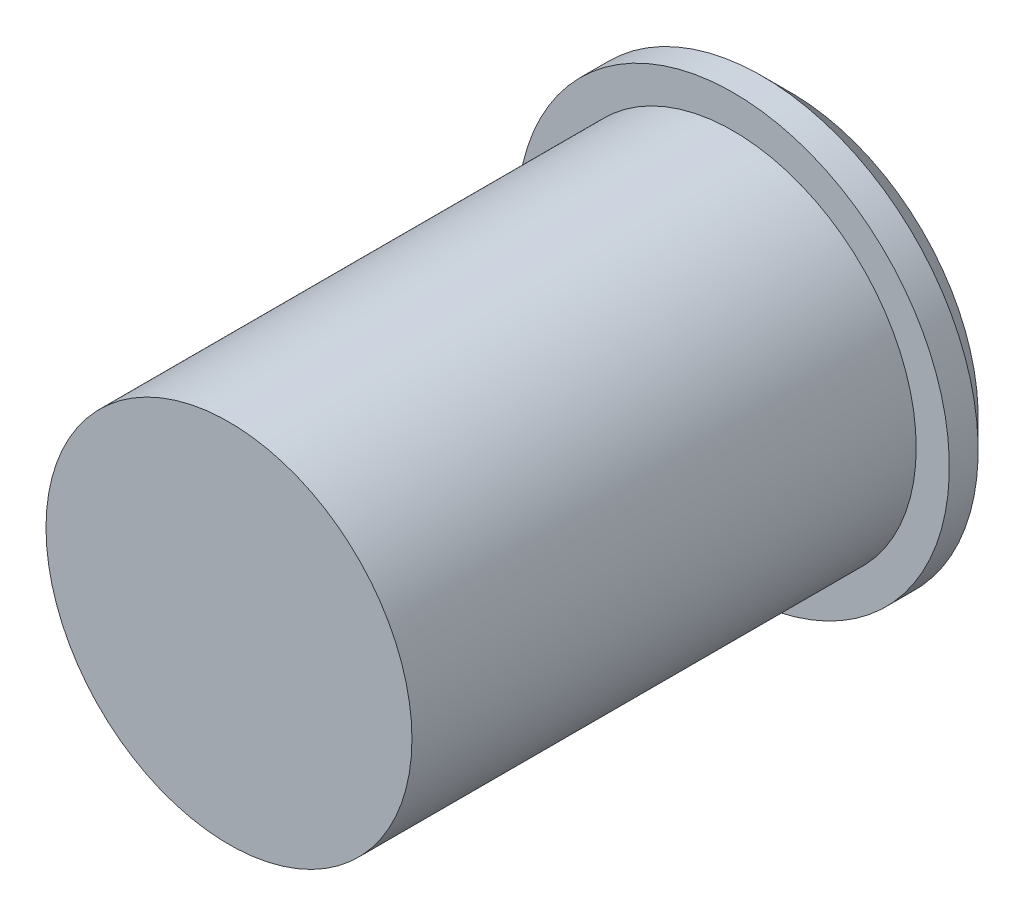
SolidWorks part; units mm, degrees
ref_plane "Front Plane" through (0, 0, 0) normal (0, 0, 1) x (1, 0, 0)
ref_plane "Top Plane" through (0, 0, 0) normal (0, 1, 0) x (1, 0, 0)
ref_plane "Right Plane" through (0, 0, 0) normal (1, 0, 0) x (0, 0, -1)
sketch "Sketch1" plane through (0, 0, 0) normal (0, 1, 0) x (1, 0, 0)
  line L0 (0, 0) -> (6.35, 0)
  line L1 (6.35, 0) -> (6.35, 17.5)
  line L2 (6.35, 17.5) -> (7.5, 17.5)
  line L3 (7.5, 17.5) -> (7.5, 18.5)
  line L4 (7.5, 18.5) -> (6.5, 19.5)
  line L5 (6.5, 19.5) -> (0, 19.5)
  line L6 (0, 19.5) -> (0, 0)
  line L7 (-7.5, 18.5) -> (-6.5, 19.5) construction
  line L8 (-7.5, 17.5) -> (-7.5, 18.5) construction
  line L9 (-6.35, 17.5) -> (-7.5, 17.5) construction
  line L10 (-6.35, 0) -> (-6.35, 17.5) construction
  line L11 (-6.5, 19.5) -> (-7.5, 19.5) construction
  line L12 (-7.5, 19.5) -> (-7.5, 18.5) construction
  line L13 (7.5, 18.5) -> (-7.5, 18.5) construction
  line L14 (-6.5, 19.5) -> (0, 19.5) construction
  line L15 (-6.35, 0) -> (0, 0) construction
  dimension "D1" = 15
  dimension "D2" = 2
  dimension "D3" = 17.5
  dimension "D4" = 45
  dimension "D5" = 12.7
revolve "Revolve2" add sketch "Sketch1" angle 360 about L6
sketch "Sketch2" plane through (0, 0, -19.5) normal (0, 0, -1) x (-1, 0, 0)
  point P0 (0, 0)
hole_wizard "3/8 (0.375) Diameter Hole1" positions "Sketch4" profile "Sketch5" hole size "3/8" standard "ANSI Inch"
sketch "Sketch4" plane through (0, 0, -19.5) normal (0, 0, -1) x (-1, 0, 0)
  point P0 (0, 0)
sketch "Sketch5" plane through (0, 0, -19.5) normal (1, 0, 0) x (0, 1, 0)
  line L0 (0, 0) -> (0, 8.8616)
  line L1 (0, 8.8616) -> (4.7625, 6)
  line L2 (4.7625, 6) -> (4.7625, 0)
  line L5 (4.7625, 0) -> (0, 0)
  line L10 (0, 8.8616) -> (-4.7625, 6) construction
  line L11 (0, -6.35) -> (0, 107.95) construction
  dimension "Hole Dia." = 9.525
  dimension "Hole Depth" = 6
  dimension "Drill Angle" = 118
